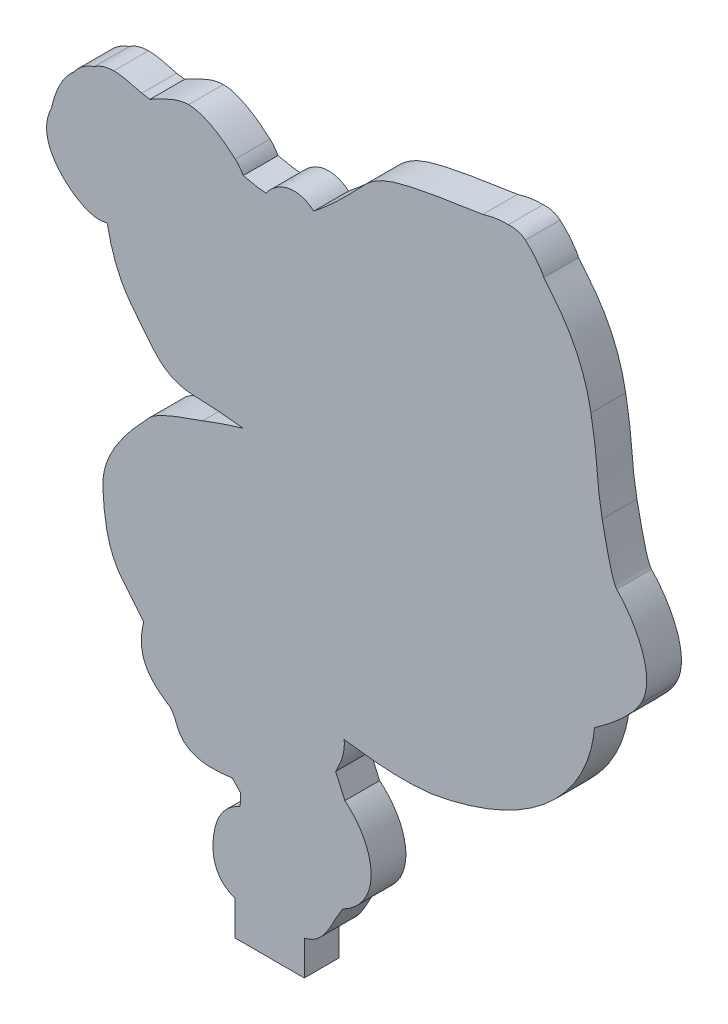
SolidWorks part; units mm, degrees
ref_plane "Front Plane" through (0, 0, 0) normal (0, 0, 1) x (1, 0, 0)
ref_plane "Top Plane" through (0, 0, 0) normal (0, 1, 0) x (1, 0, 0)
ref_plane "Right Plane" through (0, 0, 0) normal (1, 0, 0) x (0, 0, -1)
sketch "Model" plane through (0, 0, 0) normal (0, 0, 1) x (1, 0, 0)
  line L0 (258.8724, -363.7956) -> (258.3404, -363.713)
  line L1 (264.3225, -399.9794) -> (264.8876, -400.5621)
  line L2 (264.4342, -406.7579) -> (269.1376, -406.7578)
  line L3 (271.7782, -397.5499) -> (271.1682, -396.181)
  spline S0 degree 3 poles (282.6058, -359.1139) (282.1072, -359.1139) (281.6629, -359.1439) (280.9028, -359.3758) knots 0 0 0 0 1 1 1 1
  spline S1 degree 3 poles (280.9028, -359.3758) (271.5883, -360.7479) (274.754, -360.7348) (269.7234, -364.7792) knots 1 1 1 1 2 2 2 2
  spline S2 degree 3 poles (269.7234, -364.7792) (268.7295, -363.9377) (267.4104, -364.1744) (266.5573, -365.3236) knots 2 2 2 2 3 3 3 3
  spline S3 degree 3 poles (266.5573, -365.3236) (266.0018, -365.2869) (266.2521, -365.3272) (265.0515, -365.0781) knots 3 3 3 3 4 4 4 4
  spline S4 degree 3 poles (265.0515, -365.0781) (264.9233, -364.8265) (264.7473, -364.596) (264.5263, -364.3987) knots 4 4 4 4 5 5 5 5
  spline S5 degree 3 poles (264.5263, -364.3987) (264.1269, -364.0354) (262.689, -362.8164) (261.4362, -362.8161) knots 5 5 5 5 6 6 6 6
  spline S6 degree 3 poles (261.4362, -362.8161) (260.6627, -362.8317) (259.8359, -363.2708) (258.8724, -363.7956) knots 6 6 6 6 7 7 7 7
  spline S7 degree 3 poles (258.3404, -363.713) (257.1022, -363.3562) (256.6327, -363.3562) (256.4755, -363.3562) knots 8 8 8 8 9 9 9 9
  spline S8 degree 3 poles (256.4755, -363.3562) (256.009, -363.3545) (255.5534, -363.5026) (255.182, -363.7631) knots 9 9 9 9 10 10 10 10
  spline S9 degree 3 poles (255.182, -363.7631) (254.6194, -363.9475) (254.1374, -364.3086) (253.7967, -364.789) knots 10 10 10 10 11 11 11 11
  spline S10 degree 3 poles (253.7967, -364.789) (253.1126, -365.3355) (252.562, -366.51) (252.3633, -367.5542) knots 11 11 11 11 12 12 12 12
  spline S11 degree 3 poles (252.3633, -367.5542) (251.2923, -369.6011) (253.0842, -371.3132) (254.1131, -371.9161) knots 12 12 12 12 13 13 13 13
  spline S12 degree 3 poles (254.1131, -371.9161) (254.7944, -372.324) (255.3616, -372.4721) (256.0436, -372.2943) knots 13 13 13 13 14 14 14 14
  spline S13 degree 3 poles (256.0436, -372.2943) (256.3107, -373.71) (256.813, -375.173) (257.7301, -376.2928) knots 14 14 14 14 15 15 15 15
  spline S14 degree 3 poles (257.7301, -376.2928) (258.498, -377.1927) (259.0812, -378.1969) (259.9425, -378.7705) knots 15 15 15 15 16 16 16 16
  spline S15 degree 3 poles (259.9425, -378.7705) (260.7019, -379.2722) (261.5154, -379.3398) (262.211, -379.3398) knots 16 16 16 16 17 17 17 17
  spline S16 degree 3 poles (262.211, -379.3398) (262.818, -379.3398) (263.929, -379.4359) (265.0418, -379.5681) knots 17 17 17 17 18 18 18 18
  spline S17 degree 3 poles (265.0418, -379.5681) (263.4796, -380.0296) (262.8507, -380.307) (262.3605, -380.4828) knots 18 18 18 18 19 19 19 19
  spline S18 degree 3 poles (262.3605, -380.4828) (260.2826, -381.1932) (259.1333, -381.6529) (258.7225, -382.1908) knots 19 19 19 19 20 20 20 20
  spline S19 degree 3 poles (258.7225, -382.1908) (257.2004, -383.7907) (255.6448, -385.6617) (255.7607, -387.6755) knots 20 20 20 20 21 21 21 21
  spline S20 degree 3 poles (255.7607, -387.6755) (255.8678, -389.6128) (256.1339, -391.1358) (257.0844, -392.2716) knots 21 21 21 21 22 22 22 22
  spline S21 degree 3 poles (257.0844, -392.2716) (257.2857, -392.512) (257.7556, -393.0903) (258.4579, -393.962) knots 22 22 22 22 23 23 23 23
  spline S22 degree 3 poles (258.4579, -393.962) (257.9307, -396.0861) (258.8359, -397.102) (260.2656, -397.9986) knots 23 23 23 23 24 24 24 24
  spline S23 degree 3 poles (260.2656, -397.9986) (260.3694, -398.1372) (260.5502, -398.4904) (260.6429, -398.7403) knots 24 24 24 24 25 25 25 25
  spline S24 degree 3 poles (260.6429, -398.7403) (261.2099, -400.2596) (262.8754, -400.1649) (264.3225, -399.9794) knots 25 25 25 25 26 26 26 26
  spline S25 degree 3 poles (264.8876, -400.5621) (264.8761, -400.8642) (264.861, -401.1338) (264.8452, -401.3516) knots 27 27 27 27 28 28 28 28
  spline S26 degree 3 poles (264.8452, -401.3516) (263.4303, -401.9602) (263.1095, -403.2632) (263.0497, -404.357) knots 28 28 28 28 29 29 29 29
  spline S27 degree 3 poles (263.0497, -404.357) (263.0013, -405.2419) (263.2871, -406.1472) (264.1169, -406.6049) knots 29 29 29 29 30 30 30 30
  spline S28 degree 3 poles (264.1169, -406.6049) (264.2035, -406.6617) (264.3105, -406.7126) (264.4342, -406.7579) knots 30 30 30 30 31 31 31 31
  spline S29 degree 3 poles (269.1376, -406.7578) (269.5569, -406.6434) (269.7855, -406.5047) (270.0112, -406.3185) knots 32 32 32 32 33 33 33 33
  spline S30 degree 3 poles (270.0112, -406.3185) (270.6944, -405.7549) (271.0964, -404.6437) (271.6198, -403.843) knots 33 33 33 33 34 34 34 34
  spline S31 degree 3 poles (271.6198, -403.843) (274.3801, -402.3954) (273.859, -399.253) (271.7782, -397.5499) knots 34 34 34 34 35 35 35 35
  spline S32 degree 3 poles (271.1682, -396.181) (271.5506, -395.4655) (271.7903, -394.8059) (271.7325, -394.0699) knots 36 36 36 36 37 37 37 37
  spline S33 degree 3 poles (271.7325, -394.0699) (273.8858, -394.3648) (275.621, -394.521) (277.5174, -394.2955) knots 37 37 37 37 38 38 38 38
  spline S34 degree 3 poles (277.5174, -394.2955) (284.5141, -393.074) (287.9402, -389.2172) (288.3042, -385.1014) knots 38 38 38 38 39 39 39 39
  spline S35 degree 3 poles (288.3042, -385.1014) (289.413, -384.337) (290.8287, -383.1821) (291.4061, -382.1228) knots 39 39 39 39 40 40 40 40
  spline S36 degree 3 poles (291.4061, -382.1228) (292.4462, -380.2141) (290.9558, -377.6235) (289.7721, -376.4389) knots 40 40 40 40 41 41 41 41
  spline S37 degree 3 poles (289.7721, -376.4389) (289.361, -375.8714) (289.0546, -373.8832) (288.8143, -372.8924) knots 41 41 41 41 42 42 42 42
  spline S38 degree 3 poles (288.8143, -372.8924) (288.3854, -370.6784) (288.5882, -369.9812) (288.0677, -367.1711) knots 42 42 42 42 43 43 43 43
  spline S39 degree 3 poles (288.0677, -367.1711) (287.4299, -363.5002) (285.4132, -361.626) (284.9419, -360.9759) knots 43 43 43 43 44 44 44 44
  spline S40 degree 3 poles (284.9419, -360.9759) (284.8193, -360.6285) (284.2769, -359.9129) (283.7319, -359.4421) knots 44 44 44 44 45 45 45 45
  spline S41 degree 2 poles (283.7319, -359.4421) (283.311, -359.0814) (282.6058, -359.1139) knots 45 45 45 46 46 46
base flange "Base-Flange1" sketch "Model" thickness 2.3 reverse thickness direction no parameters "D1"=0.7366
sketch "Sketch9" plane through (0, 0, 0) normal (0, 0, 1) x (1, 0, 0)
  line L0 (264.4342, -406.7579) -> (269.1376, -406.7578) construction
  line L1 (269.0945, -406.7578) -> (264.4945, -406.7578)
  line L2 (269.0945, -406.7578) -> (269.0945, -409.0578)
  line L3 (269.0945, -409.0578) -> (264.4945, -409.0578)
  line L4 (264.4945, -406.7578) -> (264.4945, -409.0578)
  dimension "D1" = 4.6
  dimension "D2" = 2.3
base flange "Tab2" sketch "Sketch9" thickness 2.3 reverse thickness direction no parameters "D1"=0.7366
sketch "Bend-Lines1" [suppressed] plane through (0, 0, 0) normal (0, 1, 0) x (1, 0, 0)
sketch "Bounding-Box1" [suppressed] plane through (0, 0, 0) normal (0, 1, 0) x (1, 0, 0)
sheet metal parameters "Sheet-Metal1" thickness 2.3 parameters "D1"=0.7366
flat pattern "Flat-Pattern1" [suppressed]
sketch "Bend-Lines2" plane through (0, 0, 0) normal (0, 1, 0) x (1, 0, 0)
sketch3d "Bounding-Box2" [suppressed]
  line L0 (4.1366, 1.7753, 0) -> (12.5994, -42.4709, 0) construction
  line L1 (-32.1117, -5.1578, 0) -> (-23.6489, -49.404, 0) construction
  line L2 (4.1366, 1.7753, 0) -> (-32.1117, -5.1578, 0) construction
  line L3 (12.5994, -42.4709, 0) -> (-23.6489, -49.404, 0) construction
sheet metal parameters "Sheet-Metal3" thickness 2.3 parameters "D1"=0.7366
flat pattern "Flat-Pattern3"
sketch "Bend-Lines4" plane through (0, 0, 0) normal (0, 1, 0) x (1, 0, 0)
sketch3d "Bounding-Box4" [suppressed]
  line L0 (4.1366, 1.7753, 0) -> (13.0222, -44.6818, 0) construction
  line L1 (-32.1117, -5.1578, 0) -> (-23.226, -51.6148, 0) construction
  line L2 (4.1366, 1.7753, 0) -> (-32.1117, -5.1578, 0) construction
  line L3 (13.0222, -44.6818, 0) -> (-23.226, -51.6148, 0) construction
